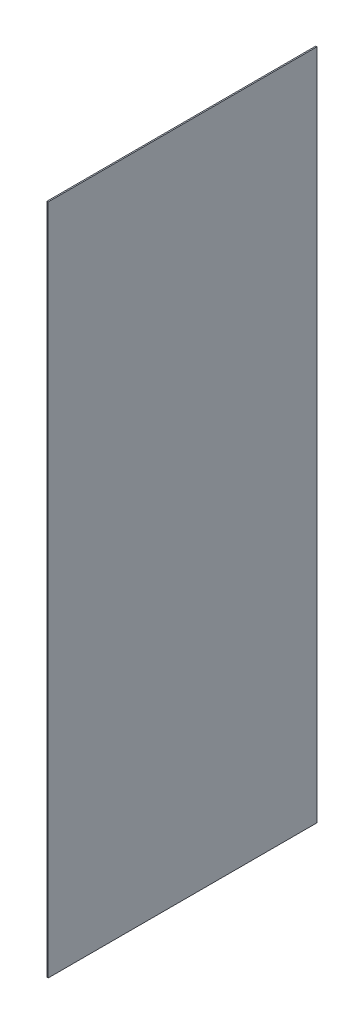
SolidWorks part; units mm, degrees
material "AISI 304"
ref_plane "Front Plane" through (0, 0, 0) normal (0, 0, 1) x (1, 0, 0)
ref_plane "Top Plane" through (0, 0, 0) normal (0, 1, 0) x (1, 0, 0)
ref_plane "Right Plane" through (0, 0, 0) normal (1, 0, 0) x (0, 0, -1)
sketch "Sketch1" plane through (0, 0, 0) normal (1, 0, 0) x (0, 0, -1)
  line L1 (130, -325) -> (-130, -325)
  line L2 (130, -325) -> (130, 325)
  line L3 (130, 325) -> (-130, 325)
  line L4 (-130, -325) -> (-130, 325)
  line L5 (130, -325) -> (-130, 325) construction
  line L6 (130, 325) -> (-130, -325) construction
  point P0 (0, 0)
  dimension "D1" = 260
  dimension "D2" = 650
base flange "Base-Flange1" sketch "Sketch1" thickness 1.2 reverse thickness direction no parameters "D1"=0.7366
sketch "Bend-Lines1" [suppressed] plane through (0, 0, 0) normal (0, 1, 0) x (1, 0, 0)
sketch "Bounding-Box1" [suppressed] plane through (0, 0, 0) normal (0, 1, 0) x (1, 0, 0)
sheet metal parameters "Sheet-Metal1" thickness 1.2 parameters "D1"=0.7366
flat pattern "Flat-Pattern1" [suppressed]
sketch "Bend-Lines2" plane through (0, 0, 0) normal (0, 1, 0) x (1, 0, 0)
sketch3d "Bounding-Box2" [suppressed]
  line L0 (-130, 325, 0) -> (-130, -325, 0) construction
  line L1 (130, 325, 0) -> (130, -325, 0) construction
  line L2 (-130, 325, 0) -> (130, 325, 0) construction
  line L3 (-130, -325, 0) -> (130, -325, 0) construction
